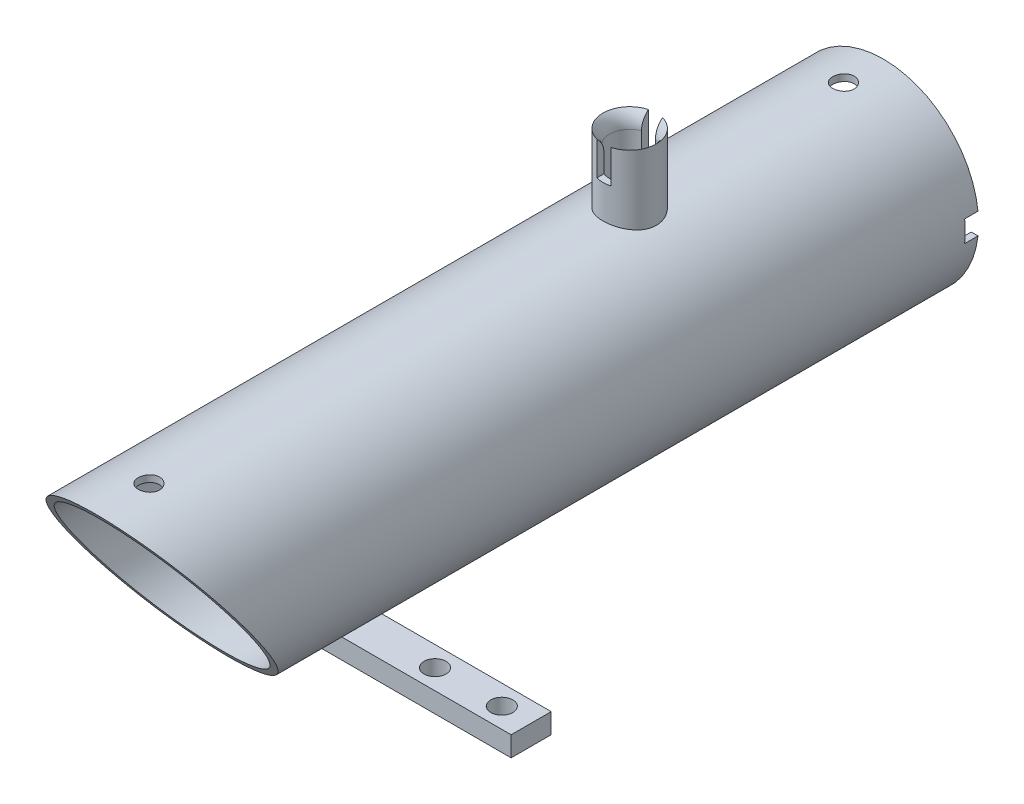
SolidWorks part; units mm, degrees
ref_plane "Front Plane" through (0, 0, 0) normal (0, 0, 1) x (1, 0, 0)
ref_plane "Top Plane" through (0, 0, 0) normal (0, 1, 0) x (1, 0, 0)
ref_plane "Right Plane" through (0, 0, 0) normal (1, 0, 0) x (0, 0, -1)
sketch "Sketch4" plane through (0, 0, 0) normal (0, 0, 1) x (1, 0, 0)
  circle A0 centre (0, 0) radius 14.25
  circle A1 centre (0, 0) radius 13.25
  dimension "D1" = 26.5
  dimension "D2" = 1
extrude "Boss-Extrude3" add sketch "Sketch4" along normal blind 118
sketch "Sketch5" plane through (0, 0, 118) normal (0, 0, 1) x (1, 0, 0)
  circle A0 centre (0, 0) radius 14.25 construction
  point P0 (0, 14.25)
  point P1 (14.25, 0)
  point P4 (-14.25, 0)
  point P5 (0, -14.25)
ref_plane "Plane1" through (0, 14.25, 118) normal (0, 1, 0) x (1, 0, 0)
sketch "Sketch6" plane through (0, 14.25, 118) normal (0, 1, 0) x (1, 0, 0)
  line L0 (-14.25, 0) -> (14.25, 0) construction
  circle A0 centre (0, 80) radius 3
  circle A1 centre (0, 80) radius 4
  dimension "D1" = 6
  dimension "D2" = 1
  dimension "D3" = 80
extrude "Boss-Extrude4" add sketch "Sketch6" along normal blind 10 and the other way blind 4
sketch "Sketch7" plane through (0, 24.25, 0) normal (0, 1, 0) x (1, 0, 0)
  circle A0 centre (0, -38) radius 3
  circle A1 centre (0, -38) radius 3 construction
extrude "Cut-Extrude1" cut sketch "Sketch7" against normal blind 20
sketch "Sketch8" plane through (0, 0, 118) normal (0, 0, 1) x (1, 0, 0)
  circle A0 centre (0, 0) radius 13.25
extrude "Cut-Extrude2" cut sketch "Sketch8" against normal up to surface (118 mm away) up to face at (14.25, 0, 0)
sketch "Sketch11" plane through (0, 14.25, 118) normal (0, 1, 0) x (1, 0, 0)
  line L0 (-14.25, 0) -> (14.25, 0) construction
  line L1 (13.25, 118) -> (-13.25, 118) construction
  circle A0 centre (0, 8) radius 1.6
  circle A1 centre (0, 112) radius 1.6
  dimension "D1" = 3.2
  dimension "D2" = 8
  dimension "D3" = 6
extrude "Cut-Extrude5" cut sketch "Sketch11" against normal blind 13
ref_plane "Plane5" through (0, -14.25, 118) normal (0, -1, 0) x (-1, 0, 0)
sketch "Sketch15" plane through (0, -14.25, 118) normal (0, -1, 0) x (-1, 0, 0)
  line L5 (0, 65) -> (0, 0) construction
  line L6 (14.25, 0) -> (14.25, 118) construction
  line L7 (14.25, 28) -> (-34.25, 28)
  line L13 (14.25, 28) -> (14.25, 34)
  line L14 (14.25, 34) -> (-34.25, 34)
  line L15 (-34.25, 28) -> (-34.25, 34)
  line L16 (-14.25, 118) -> (-14.25, 0) construction
  line L17 (-14.25, 0) -> (14.25, 0) construction
  line L18 (-34.25, 31) -> (14.25, 31) construction
  circle A2 centre (-19.85, 31) radius 1.65
  circle A3 centre (-29.85, 31) radius 1.65
  point P0 (0, 65)
  point P15 (0, 65)
  point P16 (0, 22.5)
  dimension "D4" = 3.3
  dimension "D5" = 10
  dimension "D6" = 5.6
  dimension "D1" = 20
  dimension "D2" = 6
  dimension "D3" = 28
fillet "Fillet2" radius 3 1 edges at (-3, 24.25, 38)
sketch "Sketch20" plane through (0, 14.25, 118) normal (0, 1, 0) x (1, 0, 0)
  line L1 (-1.05, 84) -> (1.05, 84)
  line L2 (-1.05, 84) -> (-1.05, 81)
  line L3 (-1.05, 81) -> (1.05, 81)
  line L4 (1.05, 84) -> (1.05, 81)
  line L5 (-1.05, 79) -> (1.05, 79)
  line L6 (-1.05, 79) -> (-1.05, 76)
  line L7 (-1.05, 76) -> (1.05, 76)
  line L8 (1.05, 79) -> (1.05, 76)
  circle A2 centre (0, 80) radius 4 construction
  circle A3 centre (0, 80) radius 4.7474
  circle A4 centre (0, 80) radius 3 construction
  point P14 (0, 79)
  point P15 (0, 81)
  dimension "D1" = 2.1
  dimension "D2" = 3
extrude "Boss-Extrude8" add sketch "Sketch15" against normal blind 3
sketch "Sketch27" plane through (0, 0, 0) normal (0, 0, -1) x (-1, 0, 0)
  circle A0 centre (0, 0) radius 13.25
extrude "Cut-Extrude15" cut sketch "Sketch27" against normal up to surface (118 mm away) up to face at (14.25, 0, 118)
sketch "Sketch28" plane through (-14.25, 0, 0) normal (-1, 0, 0) x (0, 0, 1)
  line L0 (118, 14.25) -> (98.0441, -14.25)
  line L2 (98.0441, -14.25) -> (118, -14.25)
  line L3 (118, -14.25) -> (118, 14.25)
  dimension "D1" = 35
extrude "Cut-Extrude16" cut sketch "Sketch28" against normal blind 32
sketch "Sketch29" plane through (0, 0, 0) normal (0, 0, -1) x (-1, 0, 0)
  line L1 (-17.6299, -1.6) -> (17.6299, -1.6)
  line L2 (-17.6299, -1.6) -> (-17.6299, 1.6)
  line L3 (-17.6299, 1.6) -> (17.6299, 1.6)
  line L4 (17.6299, -1.6) -> (17.6299, 1.6)
  line L5 (-17.6299, -1.6) -> (17.6299, 1.6) construction
  line L6 (-17.6299, 1.6) -> (17.6299, -1.6) construction
  point P0 (0, 0)
  dimension "D1" = 3.2
extrude "Cut-Extrude17" cut sketch "Sketch29" against normal blind 2
extrude "Cut-Extrude18" cut sketch "Sketch20" along normal blind 10 from offset 5 contours A3 L4 L1 L2 | A3 L6 L7 L8 region at (0, 14.25, 35.5) region at (0, 14.25, 40.5)
